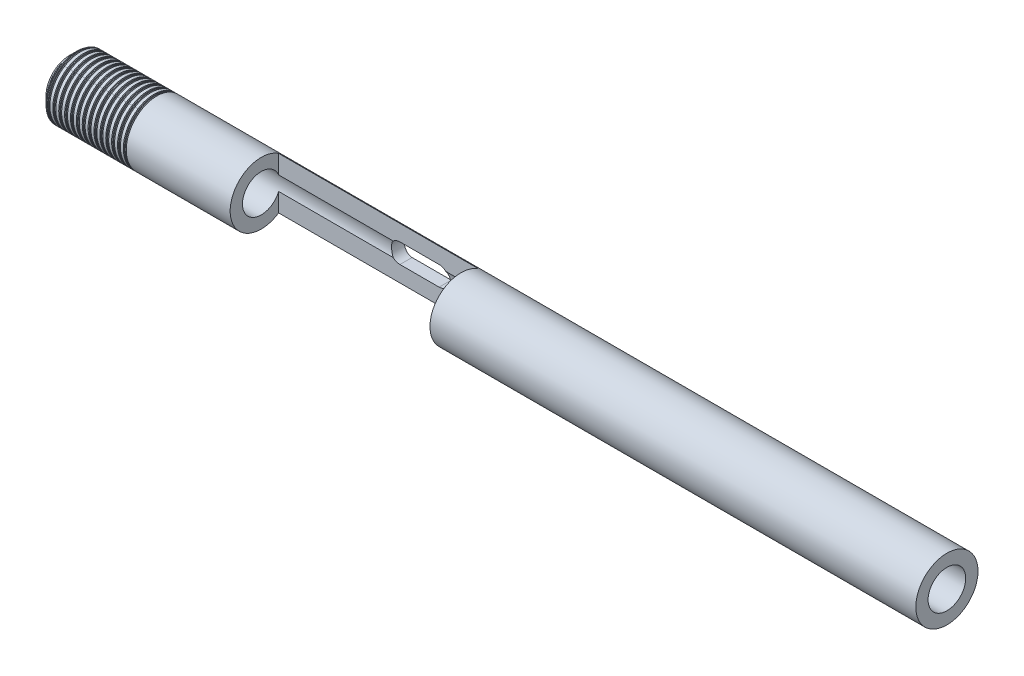
SolidWorks part; units mm, degrees
note: '?' marks a value the reader was unsure of.
ref_plane "Front Plane" through (0, 0, 0) normal (0, 0, 1) x (1, 0, 0)
ref_plane "Top Plane" through (0, 0, 0) normal (0, 1, 0) x (1, 0, 0)
ref_plane "Right Plane" through (0, 0, 0) normal (1, 0, 0) x (0, 0, -1)
ref_axis "Axis1" through (105.6189, 0, 0) along (-1, 0, 0)?
sketch "Sketch2" plane through (0, 0, 0) normal (1, 0, 0) x (0, 0, -1)
  circle A0 centre (0, 0) radius 3.9688
  circle A1 centre (0, 0) radius 2.25
  dimension "D1" = 7.9375
  dimension "D2" = 4.5
extrude "Body" add sketch "Sketch2" along normal blind 100
sketch "Sketch4" plane through (0, 0, 0) normal (0, 1, 0) x (1, 0, 0)
  line L0 (100, 3.9688) -> (0, 3.9688) construction
  line L1 (12.5, 2.2188) -> (38, 2.2188)
  line L2 (12.5, 2.2188) -> (12.5, -11.5)
  line L3 (12.5, -11.5) -> (38, -11.5)
  line L4 (38, 2.2188) -> (38, -11.5)
  dimension "D1" = 1.75
  dimension "D2" = 25.5
sketch "Sketch5" plane through (0, 0, 0) normal (-1, 0, 0) x (0, 0, 1)
  circle A0 centre (0, 0) radius 3.9688
  dimension "D1" = 7.9375
extrude "Nose" add sketch "Sketch5" along normal blind 12
sketch "Sketch7" plane through (0, 0, 0) normal (0, 0, 1) x (1, 0, 0)
  line L0 (-12, -3.9688) -> (-12.0469, -3.9688)
  line L1 (-12.0469, -3.9688) -> (-12.0937, -3.5)
  line L2 (-12.0937, -3.5) -> (-12.1875, -3.5)
  line L3 (-12.1875, -3.5) -> (-12.1875, -5.2241)
  line L4 (-12.1875, -5.2241) -> (-11.8125, -5.2241)
  line L5 (-11.8125, -5.2241) -> (-11.8125, -3.5)
  line L6 (-11.8125, -3.5) -> (-11.9062, -3.5)
  line L7 (-11.9062, -3.5) -> (-11.9531, -3.9688)
  line L9 (-11.9531, -3.9688) -> (-12, -3.9688)
  line L10 (-12.1875, -3.5) -> (-12.1875, 0) construction
  line L11 (-12.1875, 0) -> (-11.8125, 0) construction
  line L12 (-11.8125, 0) -> (-11.8125, -3.5) construction
  line L13 (-12, 0) -> (-12, -3.9688) construction
  dimension "D1" = 3.5
  dimension "D2" = 0.0469
  dimension "D3" = 0.0938
  dimension "D4" = 0.1875
sketch "Sketch8" plane through (-12, 0, 0) normal (-1, 0, 0) x (0, 0, 1)
  circle A0 centre (0, 0) radius 3.9688 construction
  circle A1 centre (0, 0) radius 3.9688
curve "Helix/Spiral1" pitch 0.75 height 12 turns 16
chamfer "Chamfer1" distance 1 angle 45 1 edges at (-12, 0, 3.9688)
sketch "Sketch10" plane through (-12, 0, 0) normal (-1, 0, 0) x (0, 0, 1)
  circle A0 centre (0, 0) radius 2.4
  dimension "D1" = 4.8
extrude "Cut-Extrude3" cut sketch "Sketch10" against normal through all contours A0
sweep "Cut-Sweep1" cut profiles "Sketch7" path "Helix/Spiral1"
extrude "cavity for slider" cut sketch "Sketch4" against normal through all and the other way through all
sketch "Sketch3" plane through (0, 0, 0) normal (0, 0, 1) x (1, 0, 0)
  line L1 (27.98, 0) -> (32.98, 0) construction
  line L2 (27.98, 1.25) -> (32.98, 1.25)
  line L3 (27.98, -1.25) -> (32.98, -1.25)
  arc A0 (27.98, 1.25) -> (27.98, -1.25) centre (27.98, 0) ccw
  arc A1 (32.98, -1.25) -> (32.98, 1.25) centre (32.98, 0) ccw
  point P2 (30.48, 0)
  point P9 (34.23, 0)
  dimension "D1" = 5
  dimension "D2" = 1.25
  dimension "D3" = 3.77
extrude "slider track for shaft of shoulder screw (2-56 threads)" cut sketch "Sketch3" against normal through all and the other way through all
equation "\"Do\"=8.5mm"
equation "\"Lo\"=10"
equation "\"screw_diam\"= 3.5mm"
equation "\"wheel_Do\"=12.5mm"
equation "\"D2@Sketch4\"=\"wheel_Do\"*2+\"clearance\""
equation "\"wheel_thickness\"=4mm"
equation "\"Collet_diameter\"=4.3"
equation "\"clearance\"= 0.5mm"
equation "\"D1@Sketch10\"=\"Collet_diameter\"+\"clearance\""
equation "\"handle_body_width\"= 10mm"
equation "\"finger_diameter\"=35"
equation "\"collet_lid_diameter\"=10"
equation "\"screw_cap_diam\"=5.15"
equation "\"handle_thickness\"=12.5mm"
equation "\"post_hole_diam\"=2"
equation "\"roll_rod_diam\"= 6.5 "
equation "\"roll_rod_length\"=6.6"
equation "\"disc_diam\"=5"
equation "\"disc_width\"=1.5"
equation "\"arm_width\"=5"
equation "\"arm_thickness\"=4.5"
equation "\"wheel_total_diam\"=30"
equation "\"spring_diam\"=4.1"
equation "\"collet_length\"= 18.75mm"
equation "\"D3@Sketch4\"=0.5*(\"wheel_Do\"*2+\"clearance\")-0.5mm"
